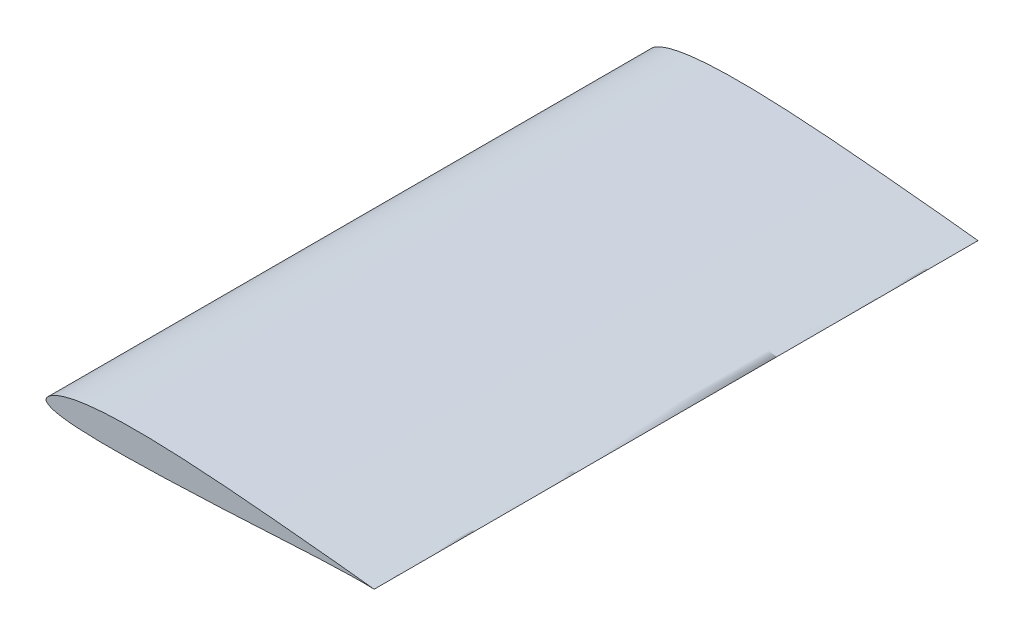
SolidWorks part; units mm, degrees
material "PLA"
ref_plane "Front Plane" through (0, 0, 0) normal (0, 0, 1) x (1, 0, 0)
ref_plane "Top Plane" through (0, 0, 0) normal (0, 1, 0) x (1, 0, 0)
ref_plane "Right Plane" through (0, 0, 0) normal (1, 0, 0) x (0, 0, -1)
other "Center of Mass"
curve "Curve1"
  spline degree 3 poles (0.9931, 0.0003, 0) (1.0017, -0.0001, 0) (0.9933, 0.0006, 0) (0.9865, 0.0015, 0) (0.9702, 0.0033, 0) (0.9504, 0.0057, 0) (0.9247, 0.0084, 0) (0.8945, 0.0115, 0) (0.8598, 0.0151, 0) (0.8211, 0.019, 0) (0.7789, 0.0232, 0) (0.7337, 0.0275, 0) (0.6861, 0.0321, 0) (0.6368, 0.0366, 0) (0.5862, 0.0409, 0) (0.535, 0.045, 0) (0.4837, 0.0487, 0) (0.4328, 0.0518, 0) (0.383, 0.0542, 0) (0.3347, 0.0559, 0) (0.2884, 0.0567, 0) (0.2445, 0.0566, 0) (0.2034, 0.0554, 0) (0.1655, 0.0532, 0) (0.1311, 0.05, 0) (0.1004, 0.0457, 0) (0.0736, 0.0405, 0) (0.0509, 0.0344, 0) (0.0323, 0.0276, 0) (0.0178, 0.0203, 0) (0.0075, 0.0127, 0) (0.0012, 0.0057, 0) (-0.0009, -0.0024, 0) (0.0055, -0.0087, 0) (0.0151, -0.0137, 0) (0.0298, -0.0183, 0) (0.0492, -0.0219, 0) (0.0733, -0.0247, 0) (0.1022, -0.0268, 0) (0.1354, -0.0283, 0) (0.1727, -0.029, 0) (0.2138, -0.0291, 0) (0.2581, -0.0286, 0) (0.3053, -0.0276, 0) (0.3549, -0.0261, 0) (0.4061, -0.0243, 0) (0.4586, -0.0222, 0) (0.5116, -0.0198, 0) (0.5646, -0.0173, 0) (0.6171, -0.0145, 0) (0.6684, -0.0117, 0) (0.7181, -0.0089, 0) (0.7655, -0.0063, 0) (0.81, -0.004, 0) (0.851, -0.0022, 0) (0.888, -0.0008, 0) (0.9203, 0.0001, 0) (0.9478, 0.0005, 0) (0.9689, 0.0007, 0) (0.9861, 0.0004, 0) (0.9931, 0.0003, 0) (1.0017, -0.0001, 0) (0.9933, 0.0006, 0) knots -0.014158 -0.006334 -0.001586 0 0.001583 0.006233 0.013742 0.023895 0.036583 0.051673 0.068989 0.088288 0.109326 0.131835 0.155529 0.180108 0.205271 0.230746 0.256241 0.281481 0.3062 0.330144 0.353088 0.37483 0.395177 0.413968 0.431081 0.446405 0.459886 0.47149 0.481241 0.489196 0.495419 0.500009 0.503132 0.506605 0.512017 0.519462 0.52915 0.541187 0.555507 0.57199 0.590481 0.610819 0.632804 0.656205 0.680761 0.706193 0.732217 0.758538 0.784859 0.810892 0.836366 0.861025 0.884574 0.906699 0.927082 0.945448 0.961521 0.975065 0.985842 0.993666 0.998414 1 1.001583 1.006233 1.013742 periodic
sketch "Sketch1" plane through (0, 0, 0) normal (0, 0, 1) x (1, 0, 0)
  line L0 (0, 0) -> (125, 0) construction
  line L1 (0, 0) -> (0, 10) construction
  spline S1 degree 3 poles (124.1407, 0.0361) (125.2147, -0.0141) (124.1568, 0.0755) (123.3063, 0.1829) (121.2715, 0.4199) (118.7984, 0.713) (115.5903, 1.0575) (111.815, 1.4483) (107.4723, 1.8919) (102.6334, 2.3782) (97.3569, 2.9043) (91.7105, 3.453) (85.7657, 4.021) (79.5958, 4.5871) (73.2734, 5.1352) (66.8704, 5.6476) (60.4567, 6.1052) (54.1028, 6.4999) (47.875, 6.808) (41.8371, 7.0212) (36.0474, 7.1229) (30.5601, 7.1062) (25.425, 6.9631) (20.6861, 6.6896) (16.3817, 6.2875) (12.5427, 5.7558) (9.1942, 5.1036) (6.3518, 4.3436) (4.0267, 3.489) (2.2186, 2.5785) (0.9318, 1.6355) (0.1415, 0.7606) (-0.1197, -0.2582) (0.6816, -1.0479) (1.8815, -1.6687) (3.7165, -2.2475) (6.1341, -2.6944) (9.1577, -3.0495) (12.7624, -3.3168) (16.9181, -3.4959) (21.5841, -3.5906) (26.7152, -3.6022) (32.2601, -3.5406) (38.1599, -3.4153) (44.3491, -3.2357) (50.7585, -3.0129) (57.3153, -2.7517) (63.9459, -2.4578) (70.5761, -2.1401) (77.1338, -1.8021) (83.5503, -1.4498) (89.7571, -1.0997) (95.6822, -0.7772) (101.2487, -0.4971) (106.3786, -0.2698) (111.004, -0.0972) (115.0409, 0.0163) (118.4772, 0.0708) (121.1134, 0.083) (123.2589, 0.0483) (124.1407, 0.0361) (125.2147, -0.0141) (124.1568, 0.0755) knots -0.014158 -0.006334 -0.001586 0 0.001583 0.006233 0.013742 0.023895 0.036583 0.051673 0.068989 0.088288 0.109326 0.131835 0.155529 0.180108 0.205271 0.230746 0.256241 0.281481 0.3062 0.330144 0.353088 0.37483 0.395177 0.413968 0.431081 0.446405 0.459886 0.47149 0.481241 0.489196 0.495419 0.500009 0.503132 0.506605 0.512017 0.519462 0.52915 0.541187 0.555507 0.57199 0.590481 0.610819 0.632804 0.656205 0.680761 0.706193 0.732217 0.758538 0.784859 0.810892 0.836366 0.861025 0.884574 0.906699 0.927082 0.945448 0.961521 0.975065 0.985842 0.993666 0.998414 1 1.001583 1.006233 1.013742 only from (125, 0) to (125, 0)
  point P2 (0, 0)
  dimension "D1" = 125
  dimension "D2" = 10
extrude "Boss-Extrude1" add sketch "Sketch1" along normal blind 230 contours S1
other "Center of Mass Reference Point1"
ref_plane "Plane1" through (0, 1.5264, 0) normal (0, 1, 0) x (1, 0, 0)
ref_plane "Plane2" through (48.3467, 0, 0) normal (1, 0, 0) x (0, 0, -1)
ref_axis "Axis1" through (48.3467, 1.5264, 241.5) along (0, 0, -1)
sketch "Sketch4" plane through (0, 0, 230) normal (0, 0, 1) x (1, 0, 0)
  line L0 (0, 11.5) -> (0, -11.5) construction
  line L1 (0, 0) -> (125, 0) construction
  dimension "D1" = 125
  dimension "23" = 23
sketch "Sketch5" plane through (0, 0, 0) normal (0, 0, -1) x (-1, 0, 0)
  line L1 (-55.9467, 2.6264) -> (-40.7467, 2.6264)
  line L2 (-55.9467, 2.6264) -> (-55.9467, 0.4264)
  line L3 (-55.9467, 0.4264) -> (-40.7467, 0.4264)
  line L4 (-40.7467, 2.6264) -> (-40.7467, 0.4264)
  point P5 (-48.3467, 1.5264)
  point P6 (-48.3467, 2.6264)
  point P10 (-55.9467, 1.5264)
  dimension "D1" = 2.2
  dimension "D2" = 15.2
extrude "Cut-Extrude1" cut sketch "Sketch5" against normal blind 220
sketch "Sketch6" plane through (0, 0, 230) normal (0, 0, 1) x (1, 0, 0)
  line L0 (48.3467, -12.65) -> (48.3467, 12.65) construction
  line L1 (68.9339, 1.5264) -> (-68.9339, 1.5264) construction
  circle A0 centre (48.3467, 1.5264) radius 50
  dimension "D1" = 100
equation "\"ChordLength\"= 125"
equation "\"d\"= 3.4"
equation "\"D1@Sketch1\"=\"ChordLength\""
equation "\"D1@Sketch4\"=\"ChordLength\""
equation "\"s\"= 10"
equation "\"t\"= 5"
equation "\"p\"= 4"
equation "\"q\"= 11"
